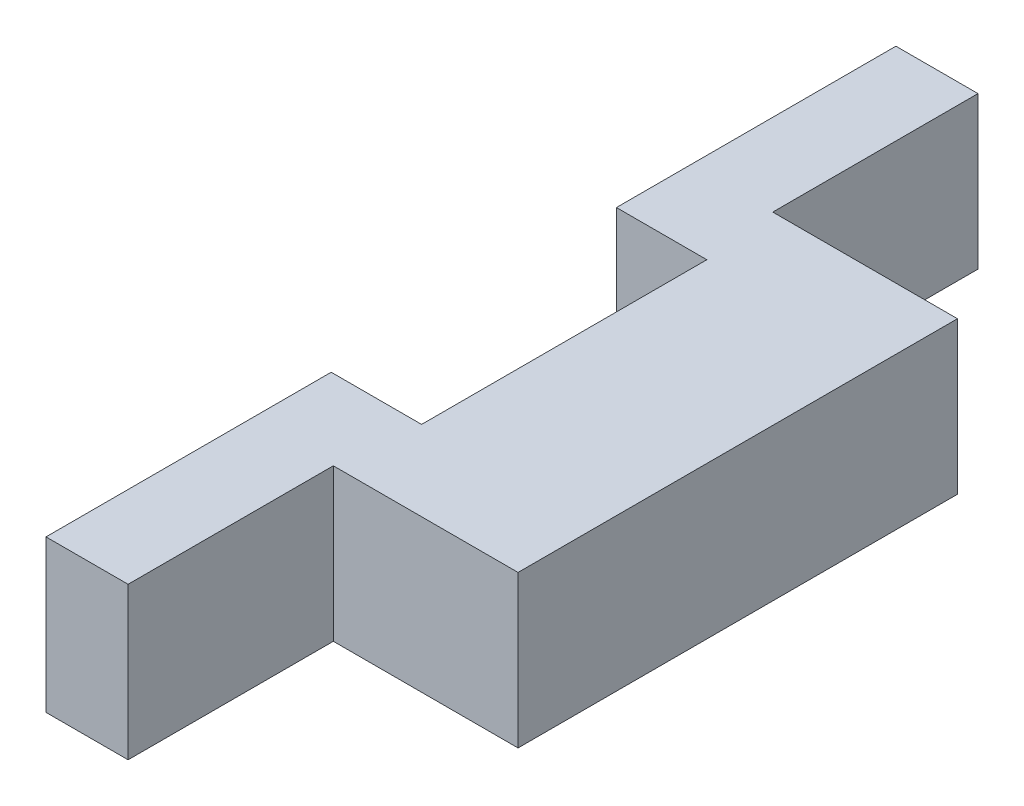
SolidWorks part; units mm, degrees
ref_plane "Front Plane" through (0, 0, 0) normal (0, 0, 1) x (1, 0, 0)
ref_plane "Top Plane" through (0, 0, 0) normal (0, 1, 0) x (1, 0, 0)
ref_plane "Right Plane" through (0, 0, 0) normal (1, 0, 0) x (0, 0, -1)
sketch "Sketch1" plane through (0, 0, 0) normal (1, 0, 0) x (0, 0, -1)
  line L0 (-24.8354, 7.8787) -> (-24.8354, -1.5287)
  line L1 (-37.5354, 7.8787) -> (15.0565, 7.8787)
  line L2 (-37.5354, 7.8787) -> (-37.5354, -1.5287)
  line L3 (-37.5354, -1.5287) -> (15.0565, -1.5287)
  line L4 (15.0565, 7.8787) -> (15.0565, -1.5287)
  line L5 (2.3565, 7.8787) -> (2.3565, -1.5287)
  dimension "D1" = 12.7
  dimension "D2" = 12.7
  dimension "D3" = 2.3565
  dimension "D4" = 24.8354
  dimension "D5" = 7.8787
  dimension "D6" = 1.5287
extrude "Boss-Extrude1" add sketch "Sketch1" along normal blind 16.51 contours L5 L1 L0 L3 region at (0, 3.175, 11.2394)
extrude "Boss-Extrude2" add sketch "Sketch1<3>" along normal blind 5.08 contours L2 L3 L0 L1 | L1 L5 L3 L4 region at (0, 3.175, 31.1854) region at (0, 3.175, -8.7065)
sketch "Sketch1<3>" plane through (0, 0, 0) normal (1, 0, 0) x (0, 0, -1) same geometry as "Sketch1"
sketch "Sketch2" plane through (0, 0, 0) normal (0, 1, 0) x (1, 0, 0)
  line L0 (0, -37.5354) -> (0, 15.0565) construction
  line L1 (0, -2.2364) -> (5.594, -2.2364)
  line L2 (0, -2.2364) -> (0, -19.8876)
  line L3 (0, -19.8876) -> (5.594, -19.8876)
  line L4 (5.594, -2.2364) -> (5.594, -19.8876)
  dimension "D1" = 5.594
  dimension "D2" = 2.2364
  dimension "D3" = 19.8876
extrude "Cut-Extrude1" cut sketch "Sketch2" along normal blind 20.828 and the other way blind 20.828
